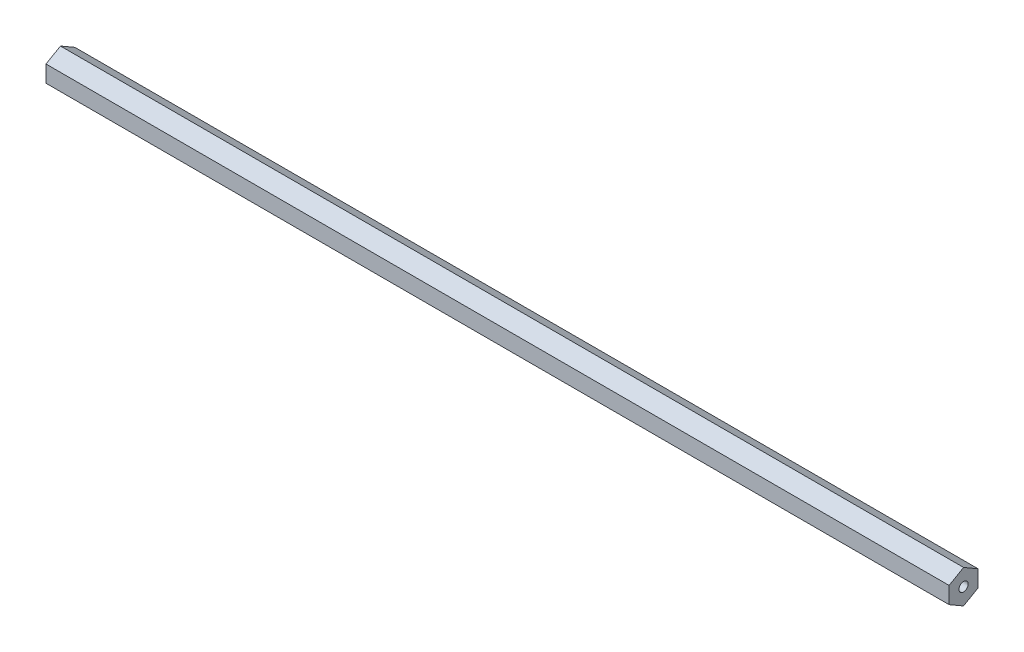
SolidWorks part; units mm, degrees
material "7075-T6 (SN)"
ref_plane "Front Plane" through (0, 0, 0) normal (0, 0, 1) x (1, 0, 0)
ref_plane "Top Plane" through (0, 0, 0) normal (0, 1, 0) x (1, 0, 0)
ref_plane "Right Plane" through (0, 0, 0) normal (1, 0, 0) x (0, 0, -1)
sketch "Sketch1" plane through (0, 0, 0) normal (1, 0, 0) x (0, 0, -1)
  line L1 (0, 7.3323) -> (-6.35, 3.6662)
  line L2 (-6.35, 3.6662) -> (-6.35, -3.6662)
  line L3 (-6.35, -3.6662) -> (0, -7.3323)
  line L4 (0, -7.3323) -> (6.35, -3.6662)
  line L5 (6.35, -3.6662) -> (6.35, 3.6662)
  line L6 (6.35, 3.6662) -> (0, 7.3323)
  circle A1 centre (0, 0) radius 6.35
  circle A2 centre (0, 0) radius 6.35 construction
  dimension "D1" = 12.7
  dimension "D2" = 12.7
extrude "Boss-Extrude1" add sketch "Sketch1" along normal mid plane 396.875 contours A1 | A1 L1 L2 | L6 L1 L2 L3 L4 L5 region at (0, 3.2816, 5.6838) region at (0, 0, 0)
hole_wizard "#10-32 Tapped Hole1" positions "3DSketch1" profile "Sketch2" tap size "#10-32" standard "ANSI Inch"
sketch3d "3DSketch1"
  line L0 (177.8, 0, 0) -> (-177.8, 0, 0) construction
  point P0 (198.4375, 0, 0)
  point P7 (-198.4375, 0, 0)
sketch "Sketch2" plane through (198.4375, 0, 0) normal (0, 1, 0) x (0, 0, -1)
  line L0 (0, 0) -> (0, 13.2428)
  line L1 (0, 13.2428) -> (2.0193, 12.0294)
  line L2 (2.0193, 12.0294) -> (2.0193, 0)
  line L5 (2.0193, 0) -> (0, 0)
  line L10 (0, 13.2428) -> (-2.0193, 12.0294) construction
  line L11 (0, -6.35) -> (0, 107.95) construction
  dimension "Tap Drill Dia." = 4.0386
  dimension "Tap Drill Depth" = 12.0294
  dimension "Drill Angle" = 118
cosmetic thread "Hole Thread1"
cosmetic thread "Hole Thread2"
